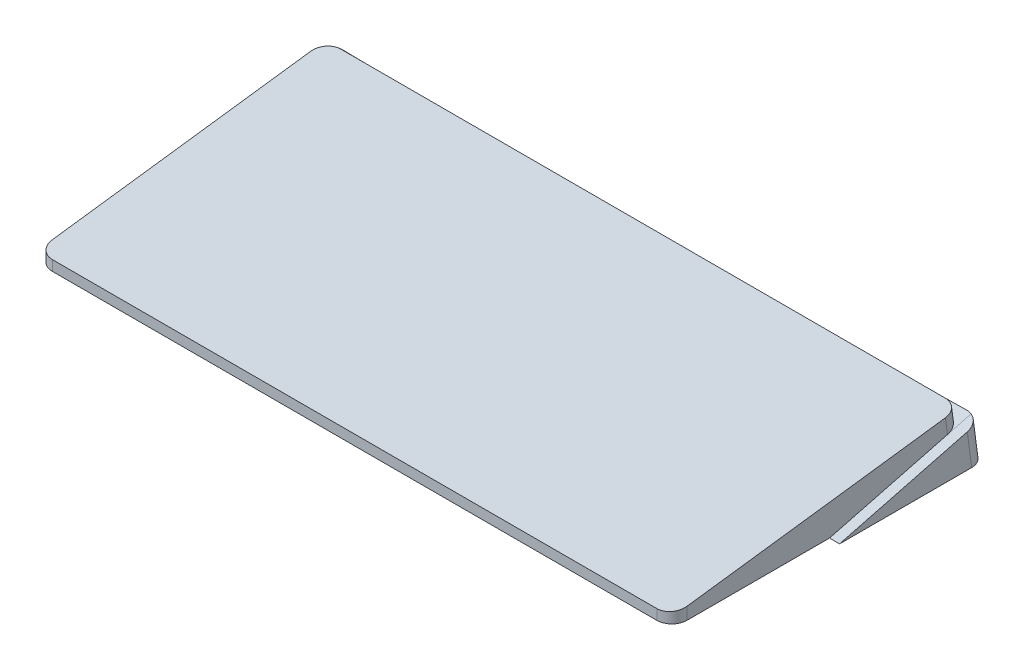
SolidWorks part; units mm, degrees
ref_plane "Front Plane" through (0, 0, 0) normal (0, 0, 1) x (1, 0, 0)
ref_plane "Top Plane" through (0, 0, 0) normal (0, 1, 0) x (1, 0, 0)
ref_plane "Right Plane" through (0, 0, 0) normal (1, 0, 0) x (0, 0, -1)
sketch "Sketch1" plane through (0, 0, 0) normal (0, 1, 0) x (1, 0, 0)
  line L1 (-157.5, 75.665) -> (157.5, 75.665)
  line L2 (-157.5, 75.665) -> (-157.5, -75.665)
  line L3 (-157.5, -75.665) -> (157.5, -75.665)
  line L4 (157.5, 75.665) -> (157.5, -75.665)
  line L5 (-157.5, 75.665) -> (157.5, -75.665) construction
  line L6 (-157.5, -75.665) -> (157.5, 75.665) construction
  point P0 (0, 0)
  dimension "D1" = 315
  dimension "D2" = 151.33
extrude "Boss-Extrude1" add sketch "Sketch1" along normal blind 25
sketch "Sketch2" plane through (0, 0, 0) normal (1, 0, 0) x (0, 0, -1)
  line L0 (-75.665, 5.077) -> (75.665, 25)
  line L1 (-75.665, 25) -> (-75.665, 0) construction
  line L2 (75.665, 25) -> (-75.665, 25)
  line L3 (-75.665, 25) -> (75.665, 25) construction
  line L4 (-75.665, 25) -> (-75.665, 5.077)
  line L5 (75.665, 0) -> (72.4298, 24.5741)
  line L6 (75.665, 25) -> (75.665, 0) construction
  line L7 (75.665, 25) -> (75.665, 0)
  dimension "D1" = 7.5
extrude "Cut-Extrude1" cut sketch "Sketch2" against normal through all both and the other way through all contours L2 L4 L0 | L7 L0 L5 region at (0, 18.359, 25.2217) region at (0, 16.5247, -74.5866)
sketch "Sketch5" plane through (0, 0, 0) normal (1, 0, 0) x (0, 0, -1)
  line L0 (2.55, 0) -> (73.2469, 18.3671)
  line L1 (75.665, 0) -> (-75.665, 0) construction
  line L2 (75.665, 0) -> (72.4298, 24.5741) construction
  line L3 (73.2469, 18.3671) -> (75.665, 0)
  line L4 (75.665, 0) -> (2.55, 0)
  line L5 (71.042, 17.7943) -> (75.665, 0) construction
  dimension "D1" = 2.55
  dimension "D2" = 18.385
extrude "Boss-Extrude2" add sketch "Sketch5" against normal mid plane 325
sketch "Sketch6" plane through (0, 9.7918, -74.3759) normal (0, 0.1305, -0.9914) x (-1, 0, 0)
  line L1 (-162.5, -9.8763) -> (162.5, -9.8763) construction
  line L2 (-42.9623, -1.1868) -> (42.9623, -1.1868) construction
  line L3 (-157.5, 8.6493) -> (-162.5, 8.6493) construction
  line L4 (0, -9.8763) -> (0, 14.9099) construction
  line L5 (157.5, 14.9099) -> (-157.5, 14.9099) construction
  line L7 (-157.5, 14.9099) -> (157.5, 14.9099)
  line L8 (-157.5, 14.9099) -> (-157.5, 28.7758)
  line L9 (-157.5, 28.7758) -> (157.5, 28.7758)
  line L10 (157.5, 14.9099) -> (157.5, 28.7758)
  line L14 (-157.5, 14.9099) -> (-157.5, 8.6493)
  line L15 (-157.5, 8.6493) -> (-162.5, 8.6493)
  line L16 (-162.5, 8.6493) -> (-162.5, -9.8763)
  line L17 (-162.5, -9.8763) -> (162.5, -9.8763)
  line L18 (162.5, -9.8763) -> (162.5, 8.6493)
  line L19 (162.5, 8.6493) -> (157.5, 8.6493)
  line L20 (157.5, 8.6493) -> (157.5, 14.9099)
  line L21 (157.5, 14.9099) -> (-157.5, 14.9099)
  line L22 (-157.5, 14.9099) -> (-157.5, 8.6493)
  line L23 (-157.5, 8.6493) -> (-162.5, 8.6493)
  line L24 (-162.5, 8.6493) -> (-162.5, -9.8763)
  line L25 (-162.5, -9.8763) -> (162.5, -9.8763)
  line L26 (162.5, -9.8763) -> (162.5, 8.6493)
  line L27 (162.5, 8.6493) -> (157.5, 8.6493)
  line L28 (157.5, 8.6493) -> (157.5, 14.9099)
  line L29 (157.5, 14.9099) -> (-157.5, 14.9099)
  arc A0 (-42.9623, -1.1868) -> (42.9623, -1.1868) centre (0, 247.1075) ccw
  arc A1 (-42.9623, -1.1868) -> (-157.5, 8.6493) centre (-157.5, -663.1407) ccw
  arc A2 (42.9623, -1.1868) -> (157.5, 8.6493) centre (157.5, -663.1407) cw
  point P5 (0, -4.8763)
  line M14 (-157.5, 14.9099) -> (-157.5, 8.6493)
  line M20 (157.5, 8.6493) -> (157.5, 14.9099)
  line M21 (157.5, 14.9099) -> (-157.5, 14.9099)
  dimension "D1" = 5
  dimension "D2" = 0
extrude "Cut-Extrude4" cut sketch "Sketch6" along direction (0, -0.2515, 0.9679) on the side against the normal blind 5 contours A0 A2 A1 M20 M21 M14 | L8 L7 L10 L9 region at (0, 17.6887, -73.3362)
fillet "Fillet2" [suppressed] radius 0.5
fillet "Fillet1" radius 7.5 6 edges at (-157.5, 2.5385, 75.665) (157.5, 2.5385, 75.665) (-162.5, 9.1836, -74.456) (162.5, 9.1836, -74.456)
sketch "Sketch4" plane through (0, 0, 0) normal (0, 1, 0) x (1, 0, 0)
  line L1 (-160.1297, 68.0505) -> (160.1297, 68.0505)
  line L2 (-160.1297, 68.0505) -> (-160.1297, -68.0505)
  line L3 (-160.1297, -68.0505) -> (160.1297, -68.0505)
  line L4 (160.1297, 68.0505) -> (160.1297, -68.0505)
  line L5 (-160.1297, 68.0505) -> (160.1297, -68.0505) construction
  line L6 (-160.1297, -68.0505) -> (160.1297, 68.0505) construction
  point P0 (0, 0)
extrude "Cut-Extrude3" [suppressed] cut sketch "Sketch4" against normal blind 10 from surface starting at face at (0, 14.5034, 4.0647)
